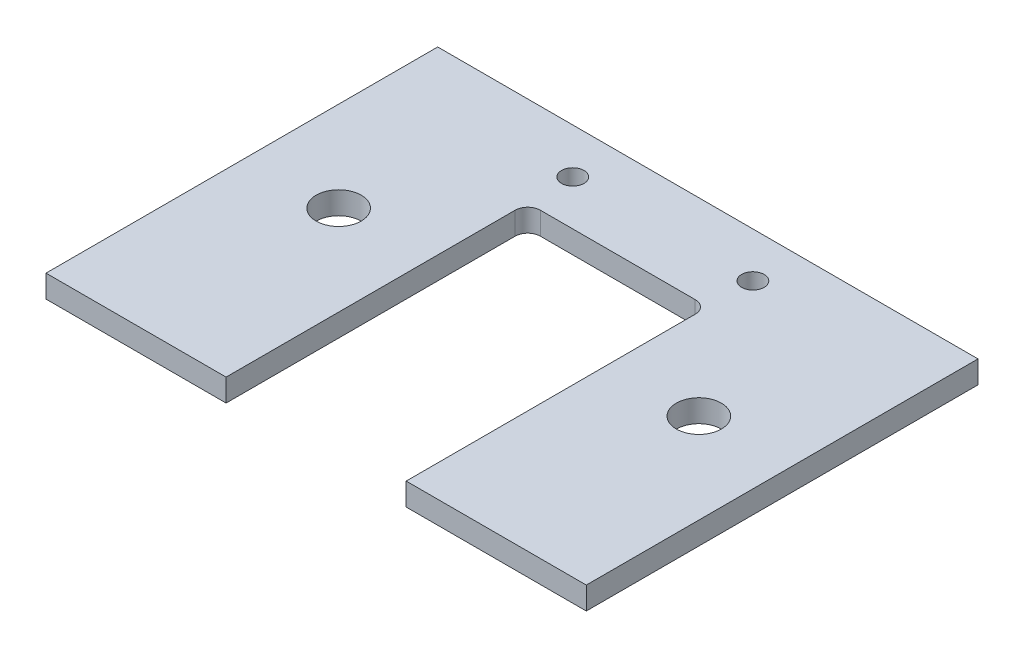
SolidWorks part; units mm, degrees
material "1060 Alloy"
ref_plane "Front Plane" through (0, 0, 0) normal (0, 0, 1) x (1, 0, 0)
ref_plane "Top Plane" through (0, 0, 0) normal (0, 1, 0) x (1, 0, 0)
ref_plane "Right Plane" through (0, 0, 0) normal (1, 0, 0) x (0, 0, -1)
sketch "Sketch1" plane through (0, 0, 0) normal (0, 1, 0) x (1, 0, 0)
  line L0 (-38.1, -42.545) -> (38.1, -42.545) construction
  line L1 (0, 0) -> (0, 12.7) construction
  line L2 (-12.7, -0.889) -> (-38.1, -0.889) construction
  line L3 (38.1, 12.7) -> (-38.1, 12.7)
  line L4 (-38.1, 12.7) -> (-38.1, -42.545)
  line L5 (-38.1, -42.545) -> (-12.7, -42.545)
  line L6 (0, 6.35) -> (-38.1, 6.35) construction
  line L7 (38.1, -0.889) -> (-38.1, -0.889) construction
  line L8 (-12.7, -42.545) -> (-12.7, 0)
  line L9 (-12.7, 0) -> (12.7, 0)
  line L10 (38.1, 12.7) -> (38.1, -42.545)
  line L11 (38.1, -42.545) -> (12.7, -42.545)
  line L12 (12.7, -42.545) -> (12.7, 0)
  line L13 (-38.1, -27.051) -> (-12.7, -27.051) construction
  line L14 (-38.1, -27.051) -> (38.1, -27.051) construction
  line L15 (-25.4, -0.889) -> (-25.4, -27.051) construction
  line L18 (38.1, 12.7) -> (-38.1, 12.7) construction
  circle A0 centre (-25.4, -13.97) radius 3.175
  circle A2 centre (25.4, -13.97) radius 3.175
  circle A3 centre (-12.7, 6.35) radius 1.5875
  circle A4 centre (12.7, 6.35) radius 1.5875
  dimension "D2" = 6.35
  dimension "D4" = 3.175
  dimension "D1" = 25.4
  dimension "D3" = 12.7
extrude "Boss-Extrude1" add sketch "Sketch1" along normal blind 3.175
fillet "Fillet1" radius 1.778 2 edges at (12.7, 1.5875, 0) (-12.7, 1.5875, 0)
